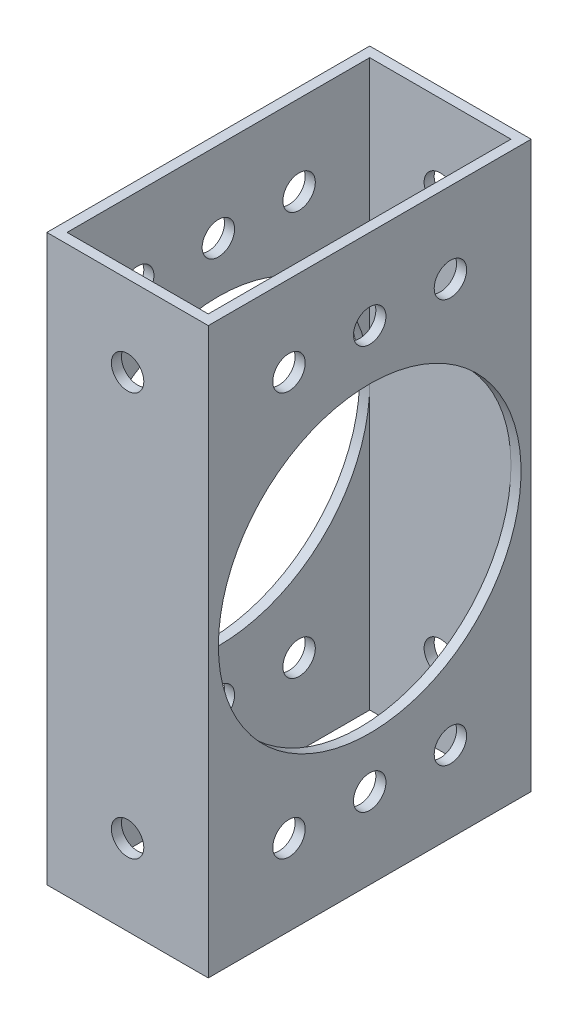
SolidWorks part; units mm, degrees
material "6061-T6 (SS)"
ref_plane "Front" through (0, 0, 0) normal (0, 0, 1) x (1, 0, 0)
ref_plane "Top" through (0, 0, 0) normal (0, 1, 0) x (1, 0, 0)
ref_plane "Right" through (0, 0, 0) normal (1, 0, 0) x (0, 0, -1)
sketch "Sketch1" plane through (0, 0, 0) normal (0, 1, 0) x (1, 0, 0)
  line L1 (12.7, 25.4) -> (-12.7, 25.4)
  line L2 (12.7, 25.4) -> (12.7, -25.4)
  line L3 (12.7, -25.4) -> (-12.7, -25.4)
  line L4 (-12.7, 25.4) -> (-12.7, -25.4)
  line L5 (12.7, 25.4) -> (-12.7, -25.4) construction
  line L6 (12.7, -25.4) -> (-12.7, 25.4) construction
  point P0 (0, 0)
  dimension "D1" = 25.4
  dimension "D2" = 50.8
extrude "Extrude-Thin1" add sketch "Sketch1" along normal up to surface (88.9 mm away) thin thin type one direction reverse wall 1.5875
sketch "Sketch4" plane through (-12.7, 0, 0) normal (-1, 0, 0) x (0, 0, 1)
  line L0 (-12.7, 12.7) -> (12.7, 12.7) construction
  line L3 (-12.7, 76.2) -> (12.7, 76.2) construction
  line L5 (-25.4, 0) -> (25.4, 0) construction
  line L6 (-25.4, 88.9) -> (25.4, 88.9) construction
  point P0 (-12.7, 76.2)
  point P2 (0, 76.2)
  point P4 (12.7, 76.2)
  point P6 (-12.7, 12.7)
  point P8 (0, 12.7)
  point P10 (12.7, 12.7)
  dimension "D1" = 12.7
  dimension "D2" = 12.7
  dimension "D3" = 12.7
  dimension "D4" = 12.7
hole_wizard "#10 Clearance Hole1" positions "Sketch4" profile "Sketch3" hole size "#10" standard "ANSI Inch" end condition through all
sketch "Sketch3" plane through (-12.7, 76.2, -12.7) normal (0, 1, 0) x (0, 0, 1)
  line L0 (0, 0) -> (0, 25.4)
  line L1 (0, 25.4) -> (2.5527, 25.4)
  line L2 (2.5527, 25.4) -> (2.5527, 0)
  line L5 (2.5527, 0) -> (0, 0)
  line L11 (0, -6.35) -> (0, 107.95) construction
  dimension "Thru Hole Dia." = 5.1054
  dimension "Thru Hole Depth" = 25.4
sketch "Sketch7" plane through (0, 0, 25.4) normal (0, 0, 1) x (1, 0, 0)
  line L0 (-12.7, 0) -> (12.7, 0) construction
  line L1 (-12.7, 88.9) -> (12.7, 88.9) construction
  point P0 (0, 12.7)
  point P2 (0, 76.2)
  dimension "D1" = 12.7
  dimension "D2" = 12.7
hole_wizard "#10 Clearance Hole2" positions "Sketch7" profile "Sketch6" hole size "#10" standard "ANSI Inch" end condition through all
sketch "Sketch6" plane through (0, 12.7, 25.4) normal (1, 0, 0) x (0, -1, 0)
  line L0 (0, 0) -> (0, 50.8)
  line L1 (0, 50.8) -> (2.5527, 50.8)
  line L2 (2.5527, 50.8) -> (2.5527, 0)
  line L5 (2.5527, 0) -> (0, 0)
  line L11 (0, -6.35) -> (0, 107.95) construction
  dimension "Thru Hole Dia." = 5.1054
  dimension "Thru Hole Depth" = 50.8
sketch "Sketch8" plane through (-12.7, 0, 0) normal (-1, 0, 0) x (0, 0, 1)
  line L0 (-25.4, 0) -> (25.4, 88.9) construction
  line L1 (25.4, 88.9) -> (25.4, 0) construction
  line L2 (-25.4, 88.9) -> (25.4, 88.9) construction
  line L3 (-25.4, 88.9) -> (-25.4, 0) construction
  line L4 (-25.4, 0) -> (25.4, 0) construction
  circle A0 centre (0, 44.45) radius 23.8125
  point P1 (10.8183, 46.4583)
  dimension "D1" = 47.625
extrude "Cut-Extrude1" cut sketch "Sketch8" against normal through all
